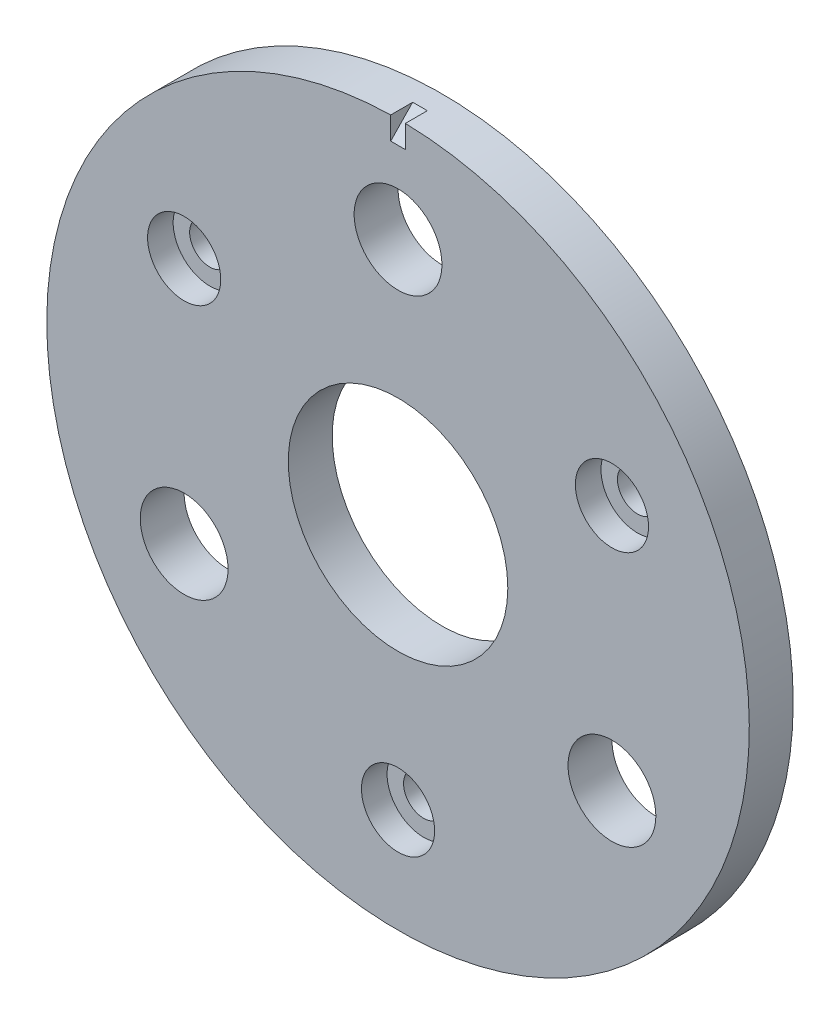
SolidWorks part; units mm, degrees
material "1.7225 (42CrMo4)"
ref_plane "Front Plane" through (0, 0, 0) normal (0, 0, 1) x (1, 0, 0)
ref_plane "Top Plane" through (0, 0, 0) normal (0, 1, 0) x (1, 0, 0)
ref_plane "Right Plane" through (0, 0, 0) normal (1, 0, 0) x (0, 0, -1)
sketch "Sketch1" plane through (0, 0, 0) normal (0, 0, 1) x (1, 0, 0)
  circle A0 centre (0, 0) radius 48
  circle A1 centre (0, 0) radius 8
  dimension "D1" = 96
  dimension "D2" = 16
extrude "EX_Carrier_Front_Plate_4mm" add sketch "Sketch1" along normal mid plane 6
sketch "Sketch2" plane through (0, 0, 3) normal (0, 0, 1) x (1, 0, 0)
  line L0 (0, 0) -> (0, 33.75) construction
  circle A0 centre (0, 33.75) radius 6
  dimension "D2" = 12
  dimension "D1" = 33.75
extrude "CUT_Pin_Hole_Ø12" cut sketch "Sketch2" against normal through all both and the other way through all contours A0
pattern_circular "PAT_Pin_Holes_3x120" count 3 over 360 about axis through (0, 0, 3) along (0, 0, 1) of "CUT_Pin_Hole_Ø12"
sketch "Sketch3" plane through (0, 0, 0) normal (1, 0, 0) x (0, 0, -1)
  line L0 (0, 48) -> (-3, 44.8893)
  line L1 (3, 48) -> (-3, 48) construction
  line L2 (-3, 48) -> (-3, -48) construction
  line L3 (-3, 44.8893) -> (-3, 48)
  line L4 (-3, 48) -> (0, 48)
extrude "Cut-Extrude1" cut sketch "Sketch3" against normal mid plane 2
ref_axis "Axis1" through (0, 0, -3.3083) along (0, 0, 1)
sketch "Sketch4" plane through (0, 0, 0) normal (0, 0, 1) x (1, 0, 0)
  circle A0 centre (0, 0) radius 15
  circle A1 centre (0, -33.75) radius 2.75
extrude "Cut-Extrude2" cut sketch "Sketch4" along normal through all
sketch "Sketch5" plane through (0, 0, 0) normal (0, 0, 1) x (1, 0, 0)
  circle A0 centre (0, 0) radius 15
  circle A1 centre (0, -33.75) radius 2.75
extrude "Cut-Extrude3" cut sketch "Sketch5" against normal through all
sketch "Sketch6" plane through (0, 0, 0) normal (0, 0, 1) x (1, 0, 0)
  circle A0 centre (29.228, 16.875) radius 2.75
  circle A1 centre (-29.228, 16.875) radius 2.75
extrude "Cut-Extrude4" cut sketch "Sketch6" along normal through all
sketch "Sketch7" plane through (0, 0, 0) normal (0, 0, 1) x (1, 0, 0)
  circle A0 centre (29.228, 16.875) radius 2.75
  circle A1 centre (-29.228, 16.875) radius 2.75
extrude "Cut-Extrude5" cut sketch "Sketch7" against normal through all
sketch "Sketch8" plane through (0, 0, 3) normal (0, 0, 1) x (1, 0, 0)
  circle A0 centre (0, -33.75) radius 5
  circle A1 centre (29.228, 16.875) radius 5
  circle A2 centre (-29.228, 16.875) radius 5
extrude "Cut-Extrude7" cut sketch "Sketch8" against normal blind 3.5
